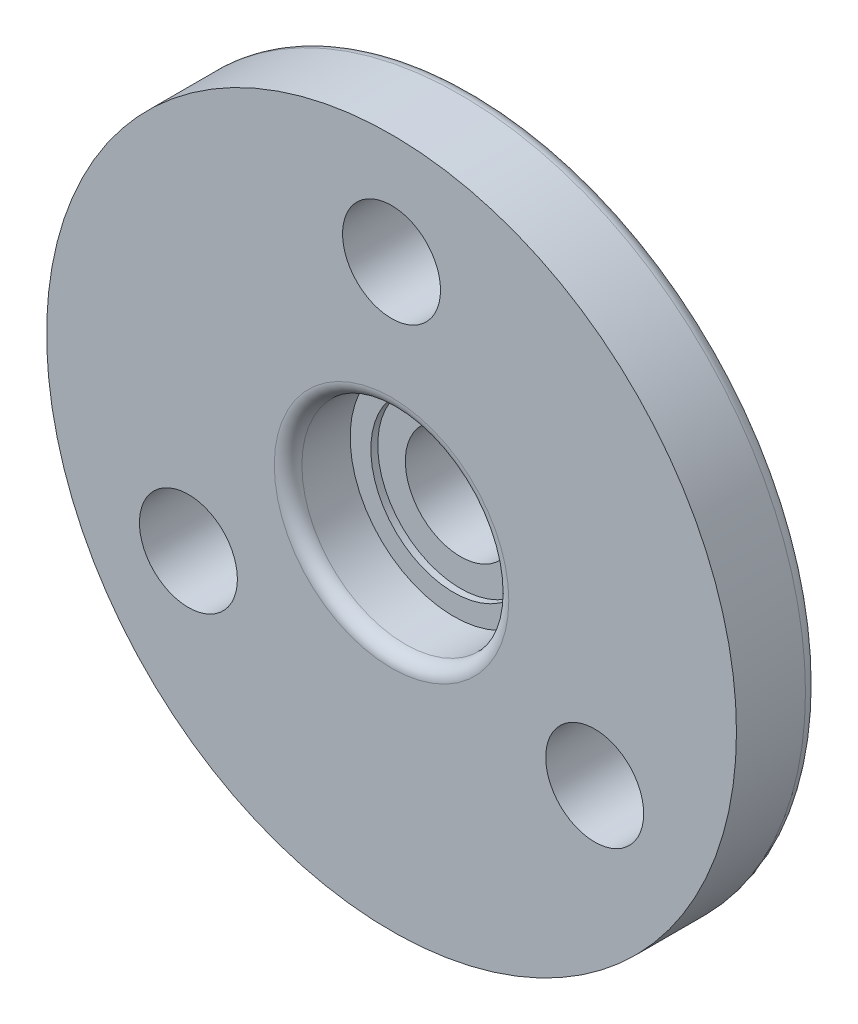
SolidWorks part; units mm, degrees
ref_plane "Ebene vorne" through (0, 0, 0) normal (0, 0, 1) x (1, 0, 0)
ref_plane "Ebene oben" through (0, 0, 0) normal (0, 1, 0) x (1, 0, 0)
ref_plane "Ebene rechts" through (0, 0, 0) normal (1, 0, 0) x (0, 0, -1)
sketch "Skizze2" plane through (0, 0, 0) normal (1, 0, 0) x (0, 0, -1)
  line L0 (0, 0) -> (99, 0) construction
  line L1 (9.5, 7) -> (8.5, 7) construction
  line L2 (9.5, 15) -> (9.5, 5) construction
  line L3 (18.5, 5) -> (9.5, 5) construction
  line L4 (18.5, 4) -> (18.5, 5) construction
  line L5 (18.5, 4) -> (7.5, 4) construction
  line L6 (7.5, 4) -> (7.5, 6) construction
  line L7 (7.5, 6) -> (7, 6) construction
  line L8 (7, 7.5) -> (7, 3) construction
  line L10 (7, 7.5) -> (2, 7.5) construction
  line L11 (2.5, 7.5) -> (2.5, 25) construction
  line L12 (8.5, 7) -> (8.5, 25) construction
  line L13 (0, 25) -> (99, 25) construction
  line L14 (0, 0) -> (99, 0) construction
  line L15 (9.5, 7) -> (8.5, 7)
  line L16 (9.5, 7) -> (9.5, 5)
  line L17 (18.5, 5) -> (9.5, 5)
  line L18 (18.5, 4) -> (18.5, 5)
  line L19 (18.5, 4) -> (7.5, 4)
  line L20 (7.5, 4) -> (7.5, 6)
  line L21 (7.5, 6) -> (7, 6)
  line L22 (7, 7.5) -> (7, 6)
  line L24 (7, 7.5) -> (2.5, 7.5)
  line L25 (2.5, 7.5) -> (2.5, 25)
  line L26 (8.5, 7) -> (8.5, 25)
  line L27 (2.5, 25) -> (8.5, 25)
revolve "Rotation1" add sketch "Skizze2" angle 360 about L14
sketch "Skizze3" plane through (0, 0, -2.5) normal (0, 0, 1) x (1, 0, 0)
  circle A0 centre (0, 0) radius 17 construction
  point P4 (0, 17)
hole_wizard "Ø7.1 (7.1) Durchmesser Bohrung1" positions "Skizze3" profile "Skizze4" hole size "Ø7.1" standard "DIN"
sketch "Skizze4" plane through (0, 17, -2.5) normal (1, 0, 0) x (0, -1, 0)
  line L0 (0, 0) -> (0, 11.6331)
  line L1 (0, 11.6331) -> (3.55, 9.5)
  line L2 (3.55, 9.5) -> (3.55, 0)
  line L5 (3.55, 0) -> (0, 0)
  line L10 (0, 11.6331) -> (-3.55, 9.5) construction
  line L11 (0, -6.35) -> (0, 107.95) construction
  dimension "Bohrerdurchmesser" = 7.1
  dimension "Bohrungstiefe" = 9.5
  dimension "Spitzenwinkel" = 118
pattern_circular "Kreismuster1" count 3 over 360 of "Ø7.1 (7.1) Durchmesser Bohrung1" reverse direction yes
fillet "Verrundung1" radius 1 3 edges at (5, 0, -18.5) (25, 0, -8.5) (7.5, 0, -2.5)
